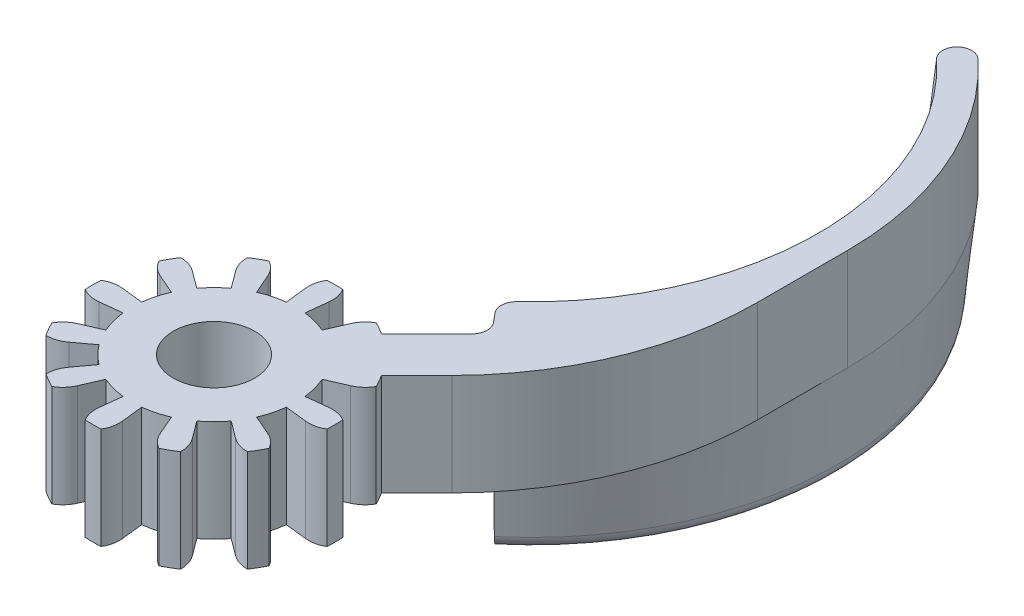
SolidWorks part; units mm, degrees
ref_plane "Plan de face" through (0, 0, 0) normal (0, 0, 1) x (1, 0, 0)
ref_plane "Plan de dessus" through (0, 0, 0) normal (0, 1, 0) x (1, 0, 0)
ref_plane "Plan de droite" through (0, 0, 0) normal (1, 0, 0) x (0, 0, -1)
sketch "Esquisse1" plane through (0, 0, 0) normal (0, 1, 0) x (1, 0, 0)
  line L0 (-18.0504, 0) -> (30.2368, 0) construction
  line L1 (0, 16.9051) -> (0, -14.3396) construction
  line L2 (0, 0) -> (-4.5652, 17.0374) construction
  line L51 (0, 0) -> (35.8316, 35.8316) construction
  line L52 (0, 0) -> (-1.8459, 16.2017) construction
  line L53 (-8.75, 40) -> (13.8918, 66.9834) construction
  line L54 (-8.75, 40) -> (13.2955, 13.7272) construction
  line L55 (-8.75, 40) -> (38.0168, 40) construction
  line L56 (10.1877, 62.5691) -> (7.9625, 59.9172)
  line L57 (10.9958, 16.4678) -> (7.9625, 20.0828)
  line L58 (22.25, 40) -> (22.25, -33.4016) construction
  line L59 (9.9946, 6.459) -> (13.4632, 9.9277)
  line L60 (6.459, 9.9946) -> (10.9074, 14.443)
  line L61 (17.25, 31.7709) -> (17.25, -36.5745) construction
  line L62 (22.25, 40) -> (22.25, 31.1409)
  line L65 (0, 0) -> (-1.1064, 16.8807) construction
  line L66 (-1.1547, 10.1344) -> (-0.9141, 8.0231)
  line L67 (1.1547, 10.1344) -> (0.9141, 8.0231)
  line L68 (4.0672, 9.354) -> (3.2199, 7.4053)
  line L70 (-8.75, 40) -> (-8.75, 0) construction
  line L72 (9.354, 4.0672) -> (7.4053, 3.2199)
  line L73 (10.1344, 1.1547) -> (8.0231, 0.9141)
  line L74 (10.1344, -1.1547) -> (8.0231, -0.9141)
  line L75 (9.354, -4.0672) -> (7.4053, -3.2199)
  line L76 (8.1993, -6.0672) -> (6.4911, -4.8032)
  line L77 (6.0672, -8.1993) -> (4.8032, -6.4911)
  line L78 (4.0672, -9.354) -> (3.2199, -7.4053)
  line L79 (1.1547, -10.1344) -> (0.9141, -8.0231)
  line L80 (-1.1547, -10.1344) -> (-0.9141, -8.0231)
  line L81 (-4.0672, -9.354) -> (-3.2199, -7.4053)
  line L82 (-6.0672, -8.1993) -> (-4.8032, -6.4911)
  line L83 (-8.1993, -6.0672) -> (-6.4911, -4.8032)
  line L84 (-9.354, -4.0672) -> (-7.4053, -3.2199)
  line L85 (-10.1344, -1.1547) -> (-8.0231, -0.9141)
  line L86 (-10.1344, 1.1547) -> (-8.0231, 0.9141)
  line L87 (-9.354, 4.0672) -> (-7.4053, 3.2199)
  line L88 (-8.1993, 6.0672) -> (-6.4911, 4.8032)
  line L89 (-6.0672, 8.1993) -> (-4.8032, 6.4911)
  line L90 (-4.0672, 9.354) -> (-3.2199, 7.4053)
  line L91 (6.0672, 8.1993) -> (4.8032, 6.4911)
  line L92 (8.1993, 6.0672) -> (6.4911, 4.8032)
  circle A0 centre (0, 0) radius 11.9 construction
  circle A26 centre (-8.75, 40) radius 25
  circle A27 centre (0, 0) radius 4
  arc A28 (7.9625, 59.9172) -> (7.9625, 20.0828) centre (-8.75, 40) cw
  arc A29 (12.3581, 62.7035) -> (22.25, 40) centre (-8.75, 40) cw
  circle A31 centre (0, 0) radius 8.075 construction
  circle A32 centre (0, 0) radius 10.2 construction
  arc A33 (-1.1547, 10.1344) -> (-0.7783, 11.8745) centre (1.6032, 10.4487) cw
  arc A34 (-0.9141, 8.0231) -> (-2.09, 7.7999) centre (0, 0) ccw
  arc A35 (0.7783, 11.8745) -> (-0.7783, 11.8745) centre (0, 0) ccw
  arc A36 (0.9141, 8.0231) -> (2.09, 7.7999) centre (0, 0) cw
  arc A37 (1.1547, 10.1344) -> (0.7783, 11.8745) centre (-1.6032, 10.4487) ccw
  arc A38 (3.2199, 7.4053) -> (2.09, 7.7999) centre (0, 0) ccw
  arc A39 (4.0672, 9.354) -> (5.2632, 10.6728) centre (6.6128, 8.2472) cw
  arc A40 (10.9074, 14.443) -> (10.9958, 16.4678) centre (9.8468, 15.5036) ccw
  arc A41 (5.2632, 10.6728) -> (6.459, 9.9946) centre (0, 0) cw
  arc A42 (9.9946, 6.459) -> (10.6728, 5.2632) centre (0, 0) cw
  arc A43 (13.4632, 9.9277) -> (22.25, 31.1409) centre (-7.75, 31.1409) ccw
  arc A46 (9.354, 4.0672) -> (10.6728, 5.2632) centre (8.2472, 6.6128) ccw
  arc A47 (7.4053, 3.2199) -> (7.7999, 2.09) centre (0, 0) cw
  arc A48 (8.0231, 0.9141) -> (7.7999, 2.09) centre (0, 0) ccw
  arc A49 (10.1344, 1.1547) -> (11.8745, 0.7783) centre (10.4487, -1.6032) cw
  arc A50 (11.8745, -0.7783) -> (11.8745, 0.7783) centre (0, 0) ccw
  arc A51 (10.1344, -1.1547) -> (11.8745, -0.7783) centre (10.4487, 1.6032) ccw
  arc A52 (8.0231, -0.9141) -> (7.7999, -2.09) centre (0, 0) cw
  arc A53 (7.4053, -3.2199) -> (7.7999, -2.09) centre (0, 0) ccw
  arc A54 (9.354, -4.0672) -> (10.6728, -5.2632) centre (8.2472, -6.6128) cw
  arc A55 (9.8945, -6.6113) -> (10.6728, -5.2632) centre (0, 0) ccw
  arc A56 (8.1993, -6.0672) -> (9.8945, -6.6113) centre (9.8504, -3.8359) ccw
  arc A57 (6.4911, -4.8032) -> (5.7099, -5.7099) centre (0, 0) cw
  arc A58 (4.8032, -6.4911) -> (5.7099, -5.7099) centre (0, 0) ccw
  arc A59 (6.0672, -8.1993) -> (6.6113, -9.8945) centre (3.8359, -9.8504) cw
  arc A60 (5.2632, -10.6728) -> (6.6113, -9.8945) centre (0, 0) ccw
  arc A61 (4.0672, -9.354) -> (5.2632, -10.6728) centre (6.6128, -8.2472) ccw
  arc A62 (3.2199, -7.4053) -> (2.09, -7.7999) centre (0, 0) cw
  arc A63 (0.9141, -8.0231) -> (2.09, -7.7999) centre (0, 0) ccw
  arc A64 (1.1547, -10.1344) -> (0.7783, -11.8745) centre (-1.6032, -10.4487) cw
  arc A65 (-0.7783, -11.8745) -> (0.7783, -11.8745) centre (0, 0) ccw
  arc A66 (-1.1547, -10.1344) -> (-0.7783, -11.8745) centre (1.6032, -10.4487) ccw
  arc A67 (-0.9141, -8.0231) -> (-2.09, -7.7999) centre (0, 0) cw
  arc A68 (-3.2199, -7.4053) -> (-2.09, -7.7999) centre (0, 0) ccw
  arc A69 (-4.0672, -9.354) -> (-5.2632, -10.6728) centre (-6.6128, -8.2472) cw
  arc A70 (-6.6113, -9.8945) -> (-5.2632, -10.6728) centre (0, 0) ccw
  arc A71 (-6.0672, -8.1993) -> (-6.6113, -9.8945) centre (-3.8359, -9.8504) ccw
  arc A72 (-4.8032, -6.4911) -> (-5.7099, -5.7099) centre (0, 0) cw
  arc A73 (-6.4911, -4.8032) -> (-5.7099, -5.7099) centre (0, 0) ccw
  arc A74 (-8.1993, -6.0672) -> (-9.8945, -6.6113) centre (-9.8504, -3.8359) cw
  arc A75 (-10.6728, -5.2632) -> (-9.8945, -6.6113) centre (0, 0) ccw
  arc A76 (-9.354, -4.0672) -> (-10.6728, -5.2632) centre (-8.2472, -6.6128) ccw
  arc A77 (-7.4053, -3.2199) -> (-7.7999, -2.09) centre (0, 0) cw
  arc A78 (-8.0231, -0.9141) -> (-7.7999, -2.09) centre (0, 0) ccw
  arc A79 (-10.1344, -1.1547) -> (-11.8745, -0.7783) centre (-10.4487, 1.6032) cw
  arc A80 (-11.8745, 0.7783) -> (-11.8745, -0.7783) centre (0, 0) ccw
  arc A81 (-10.1344, 1.1547) -> (-11.8745, 0.7783) centre (-10.4487, -1.6032) ccw
  arc A82 (-8.0231, 0.9141) -> (-7.7999, 2.09) centre (0, 0) cw
  arc A83 (-7.4053, 3.2199) -> (-7.7999, 2.09) centre (0, 0) ccw
  arc A84 (-9.354, 4.0672) -> (-10.6728, 5.2632) centre (-8.2472, 6.6128) cw
  arc A85 (-9.8945, 6.6113) -> (-10.6728, 5.2632) centre (0, 0) ccw
  arc A86 (-8.1993, 6.0672) -> (-9.8945, 6.6113) centre (-9.8504, 3.8359) ccw
  arc A87 (-6.4911, 4.8032) -> (-5.7099, 5.7099) centre (0, 0) cw
  arc A88 (-4.8032, 6.4911) -> (-5.7099, 5.7099) centre (0, 0) ccw
  arc A89 (-6.0672, 8.1993) -> (-6.6113, 9.8945) centre (-3.8359, 9.8504) cw
  arc A90 (-5.2632, 10.6728) -> (-6.6113, 9.8945) centre (0, 0) ccw
  arc A91 (-4.0672, 9.354) -> (-5.2632, 10.6728) centre (-6.6128, 8.2472) ccw
  arc A92 (-3.2199, 7.4053) -> (-2.09, 7.7999) centre (0, 0) cw
  arc A93 (6.0672, 8.1993) -> (6.6113, 9.8945) centre (3.8359, 9.8504) ccw
  arc A94 (4.8032, 6.4911) -> (5.7099, 5.7099) centre (0, 0) cw
  arc A95 (6.4911, 4.8032) -> (5.7099, 5.7099) centre (0, 0) ccw
  arc A96 (8.1993, 6.0672) -> (9.8945, 6.6113) centre (9.8504, 3.8359) cw
  arc A99 (12.3581, 62.7035) -> (10.1877, 62.5691) centre (11.3368, 61.6049) ccw
  arc A100 (6.6113, 9.8945) -> (5.2632, 10.6728) centre (0, 0) ccw
  arc A101 (10.6728, 5.2632) -> (9.8945, 6.6113) centre (0, 0) ccw
  point P14 (0, 11.9)
  point P37 (22.25, 18.7145)
  point P46 (17.25, 20.2855)
  point P52 (10.855, 16.6356)
  point P65 (17.25, 23.2668)
  point P90 (11.1764, 63.7474)
  point P133 (0, 0)
  point P170 (0, 0)
  dimension "D2" = 20.4
  dimension "D4" = 23.8
  dimension "D6" = 6.5
  dimension "D8" = 40
  dimension "D9" = 50
  dimension "D10" = 8
  dimension "D11" = 5
  dimension "D12" = 26
  dimension "D15" = 45
  dimension "D5" = 16.15
  dimension "D18" = 12
  dimension "D19" = 8.75
  dimension "D20" = 30
  dimension "D21" = 1.5
  dimension "D3" = 15
  dimension "D7" = 3.75
  dimension "D13" = 50
  dimension "D14" = 50
  dimension "D16" = 5
  dimension "D17" = 5
extrude "Boss.-Extru.1" add sketch "Esquisse1" along normal blind 10 contours A92 L90 A91 A90 A89 L89 A88 A87 L88 A86 A85 A84 L87 A83 A82 L86 A81 A80 A79 L85 A78 A77 L84 A76 A75 A74 L83 A73 A72 L82 A71 A70 A69 L81 A68 A67 L80 A66 A65 A64 L79 A63 A62 L78 A61 A60 A59 L77 A58 A57 L76
sketch "Esquisse2" plane through (0, 0, 0) normal (0, -1, 0) x (1, 0, 0)
  line L28 (22.25, -40) -> (22.25, -31.1409)
  line L29 (13.4632, -9.9277) -> (9.9946, -6.459)
  line L30 (9.354, -4.0672) -> (7.4053, -3.2199)
  line L31 (8.0231, -0.9141) -> (10.1344, -1.1547)
  line L32 (10.1344, 1.1547) -> (8.0231, 0.9141)
  line L33 (7.4053, 3.2199) -> (9.354, 4.0672)
  line L34 (8.1993, 6.0672) -> (6.4911, 4.8032)
  line L35 (4.8032, 6.4911) -> (6.0672, 8.1993)
  line L36 (4.0672, 9.354) -> (3.2199, 7.4053)
  line L37 (0.9141, 8.0231) -> (1.1547, 10.1344)
  line L38 (-1.1547, 10.1344) -> (-0.9141, 8.0231)
  line L39 (-3.2199, 7.4053) -> (-4.0672, 9.354)
  line L40 (-6.0672, 8.1993) -> (-4.8032, 6.4911)
  line L41 (-6.4911, 4.8032) -> (-8.1993, 6.0672)
  line L42 (-9.354, 4.0672) -> (-7.4053, 3.2199)
  line L43 (-8.0231, 0.9141) -> (-10.1344, 1.1547)
  line L44 (-10.1344, -1.1547) -> (-8.0231, -0.9141)
  line L45 (-7.4053, -3.2199) -> (-9.354, -4.0672)
  line L46 (-8.1993, -6.0672) -> (-6.4911, -4.8032)
  line L47 (-4.8032, -6.4911) -> (-6.0672, -8.1993)
  line L48 (-4.0672, -9.354) -> (-3.2199, -7.4053)
  line L49 (-0.9141, -8.0231) -> (-1.1547, -10.1344)
  line L50 (1.1547, -10.1344) -> (0.9141, -8.0231)
  line L51 (3.2199, -7.4053) -> (4.0672, -9.354)
  line L52 (6.459, -9.9946) -> (10.9074, -14.443)
  line L54 (10.9958, -16.4678) -> (7.9625, -20.0828)
  line L55 (7.9625, -59.9172) -> (10.1877, -62.5691)
  line L56 (22.25, -40) -> (22.25, -31.1409)
  line L57 (13.4632, -9.9277) -> (9.9946, -6.459)
  line L58 (9.354, -4.0672) -> (7.4053, -3.2199)
  line L59 (8.0231, -0.9141) -> (10.1344, -1.1547)
  line L60 (10.1344, 1.1547) -> (8.0231, 0.9141)
  line L61 (7.4053, 3.2199) -> (9.354, 4.0672)
  line L62 (8.1993, 6.0672) -> (6.4911, 4.8032)
  line L63 (4.8032, 6.4911) -> (6.0672, 8.1993)
  line L64 (4.0672, 9.354) -> (3.2199, 7.4053)
  line L65 (0.9141, 8.0231) -> (1.1547, 10.1344)
  line L66 (-1.1547, 10.1344) -> (-0.9141, 8.0231)
  line L67 (-3.2199, 7.4053) -> (-4.0672, 9.354)
  line L68 (-6.0672, 8.1993) -> (-4.8032, 6.4911)
  line L69 (-6.4911, 4.8032) -> (-8.1993, 6.0672)
  line L70 (-9.354, 4.0672) -> (-7.4053, 3.2199)
  line L71 (-8.0231, 0.9141) -> (-10.1344, 1.1547)
  line L72 (-10.1344, -1.1547) -> (-8.0231, -0.9141)
  line L73 (-7.4053, -3.2199) -> (-9.354, -4.0672)
  line L74 (-8.1993, -6.0672) -> (-6.4911, -4.8032)
  line L75 (-4.8032, -6.4911) -> (-6.0672, -8.1993)
  line L76 (-4.0672, -9.354) -> (-3.2199, -7.4053)
  line L77 (-0.9141, -8.0231) -> (-1.1547, -10.1344)
  line L78 (1.1547, -10.1344) -> (0.9141, -8.0231)
  line L79 (3.2199, -7.4053) -> (4.0672, -9.354)
  line L80 (6.459, -9.9946) -> (10.9074, -14.443)
  line L82 (10.9958, -16.4678) -> (7.9625, -20.0828)
  line L83 (7.9625, -59.9172) -> (10.1877, -62.5691)
  arc A0 (22.25, -40) -> (11.1561, -16.2356) centre (-8.75, -40) ccw
  arc A51 (10.9958, -16.4678) -> (10.9074, -14.443) centre (9.8468, -15.5036) ccw
  arc A52 (10.9958, -16.4678) -> (10.9074, -14.443) centre (9.8468, -15.5036) ccw
  arc A53 (12.3581, -62.7035) -> (22.25, -40) centre (-8.75, -40) ccw
  arc A54 (22.25, -31.1409) -> (13.4632, -9.9277) centre (-7.75, -31.1409) ccw
  arc A55 (9.9946, -6.459) -> (10.6728, -5.2632) centre (0, 0) ccw
  arc A56 (10.6728, -5.2632) -> (9.354, -4.0672) centre (8.2472, -6.6128) ccw
  arc A57 (7.4053, -3.2199) -> (8.0231, -0.9141) centre (0, 0) ccw
  arc A58 (10.1344, -1.1547) -> (11.8745, -0.7783) centre (10.4487, 1.6032) ccw
  arc A59 (11.8745, -0.7783) -> (11.8745, 0.7783) centre (0, 0) ccw
  arc A60 (11.8745, 0.7783) -> (10.1344, 1.1547) centre (10.4487, -1.6032) ccw
  arc A61 (8.0231, 0.9141) -> (7.4053, 3.2199) centre (0, 0) ccw
  arc A62 (9.354, 4.0672) -> (10.6728, 5.2632) centre (8.2472, 6.6128) ccw
  arc A63 (10.6728, 5.2632) -> (9.8945, 6.6113) centre (0, 0) ccw
  arc A64 (9.8945, 6.6113) -> (8.1993, 6.0672) centre (9.8504, 3.8359) ccw
  arc A65 (6.4911, 4.8032) -> (4.8032, 6.4911) centre (0, 0) ccw
  arc A66 (6.0672, 8.1993) -> (6.6113, 9.8945) centre (3.8359, 9.8504) ccw
  arc A67 (6.6113, 9.8945) -> (5.2632, 10.6728) centre (0, 0) ccw
  arc A68 (5.2632, 10.6728) -> (4.0672, 9.354) centre (6.6128, 8.2472) ccw
  arc A69 (3.2199, 7.4053) -> (0.9141, 8.0231) centre (0, 0) ccw
  arc A70 (1.1547, 10.1344) -> (0.7783, 11.8745) centre (-1.6032, 10.4487) ccw
  arc A71 (0.7783, 11.8745) -> (-0.7783, 11.8745) centre (0, 0) ccw
  arc A72 (-0.7783, 11.8745) -> (-1.1547, 10.1344) centre (1.6032, 10.4487) ccw
  arc A73 (-0.9141, 8.0231) -> (-3.2199, 7.4053) centre (0, 0) ccw
  arc A74 (-4.0672, 9.354) -> (-5.2632, 10.6728) centre (-6.6128, 8.2472) ccw
  arc A75 (-5.2632, 10.6728) -> (-6.6113, 9.8945) centre (0, 0) ccw
  arc A76 (-6.6113, 9.8945) -> (-6.0672, 8.1993) centre (-3.8359, 9.8504) ccw
  arc A77 (-4.8032, 6.4911) -> (-6.4911, 4.8032) centre (0, 0) ccw
  arc A78 (-8.1993, 6.0672) -> (-9.8945, 6.6113) centre (-9.8504, 3.8359) ccw
  arc A79 (-9.8945, 6.6113) -> (-10.6728, 5.2632) centre (0, 0) ccw
  arc A80 (-10.6728, 5.2632) -> (-9.354, 4.0672) centre (-8.2472, 6.6128) ccw
  arc A81 (-7.4053, 3.2199) -> (-8.0231, 0.9141) centre (0, 0) ccw
  arc A82 (-10.1344, 1.1547) -> (-11.8745, 0.7783) centre (-10.4487, -1.6032) ccw
  arc A83 (-11.8745, 0.7783) -> (-11.8745, -0.7783) centre (0, 0) ccw
  arc A84 (-11.8745, -0.7783) -> (-10.1344, -1.1547) centre (-10.4487, 1.6032) ccw
  arc A85 (-8.0231, -0.9141) -> (-7.4053, -3.2199) centre (0, 0) ccw
  arc A86 (-9.354, -4.0672) -> (-10.6728, -5.2632) centre (-8.2472, -6.6128) ccw
  arc A87 (-10.6728, -5.2632) -> (-9.8945, -6.6113) centre (0, 0) ccw
  arc A88 (-9.8945, -6.6113) -> (-8.1993, -6.0672) centre (-9.8504, -3.8359) ccw
  arc A89 (-6.4911, -4.8032) -> (-4.8032, -6.4911) centre (0, 0) ccw
  arc A90 (-6.0672, -8.1993) -> (-6.6113, -9.8945) centre (-3.8359, -9.8504) ccw
  arc A91 (-6.6113, -9.8945) -> (-5.2632, -10.6728) centre (0, 0) ccw
  arc A92 (-5.2632, -10.6728) -> (-4.0672, -9.354) centre (-6.6128, -8.2472) ccw
  arc A93 (-3.2199, -7.4053) -> (-0.9141, -8.0231) centre (0, 0) ccw
  arc A94 (-1.1547, -10.1344) -> (-0.7783, -11.8745) centre (1.6032, -10.4487) ccw
  arc A95 (-0.7783, -11.8745) -> (0.7783, -11.8745) centre (0, 0) ccw
  arc A96 (0.7783, -11.8745) -> (1.1547, -10.1344) centre (-1.6032, -10.4487) ccw
  arc A97 (0.9141, -8.0231) -> (3.2199, -7.4053) centre (0, 0) ccw
  arc A98 (4.0672, -9.354) -> (5.2632, -10.6728) centre (6.6128, -8.2472) ccw
  arc A99 (5.2632, -10.6728) -> (6.459, -9.9946) centre (0, 0) ccw
  arc A104 (7.9625, -59.9172) -> (7.9625, -20.0828) centre (-8.75, -40) ccw
  arc A105 (10.1877, -62.5691) -> (12.3581, -62.7035) centre (11.3368, -61.6049) ccw
  arc A106 (12.3581, -62.7035) -> (22.25, -40) centre (-8.75, -40) ccw
  arc A107 (22.25, -31.1409) -> (13.4632, -9.9277) centre (-7.75, -31.1409) ccw
  arc A108 (9.9946, -6.459) -> (10.6728, -5.2632) centre (0, 0) ccw
  arc A109 (10.6728, -5.2632) -> (9.354, -4.0672) centre (8.2472, -6.6128) ccw
  arc A110 (7.4053, -3.2199) -> (8.0231, -0.9141) centre (0, 0) ccw
  arc A111 (10.1344, -1.1547) -> (11.8745, -0.7783) centre (10.4487, 1.6032) ccw
  arc A112 (11.8745, -0.7783) -> (11.8745, 0.7783) centre (0, 0) ccw
  arc A113 (11.8745, 0.7783) -> (10.1344, 1.1547) centre (10.4487, -1.6032) ccw
  arc A114 (8.0231, 0.9141) -> (7.4053, 3.2199) centre (0, 0) ccw
  arc A115 (9.354, 4.0672) -> (10.6728, 5.2632) centre (8.2472, 6.6128) ccw
  arc A116 (10.6728, 5.2632) -> (9.8945, 6.6113) centre (0, 0) ccw
  arc A117 (9.8945, 6.6113) -> (8.1993, 6.0672) centre (9.8504, 3.8359) ccw
  arc A118 (6.4911, 4.8032) -> (4.8032, 6.4911) centre (0, 0) ccw
  arc A119 (6.0672, 8.1993) -> (6.6113, 9.8945) centre (3.8359, 9.8504) ccw
  arc A120 (6.6113, 9.8945) -> (5.2632, 10.6728) centre (0, 0) ccw
  arc A121 (5.2632, 10.6728) -> (4.0672, 9.354) centre (6.6128, 8.2472) ccw
  arc A122 (3.2199, 7.4053) -> (0.9141, 8.0231) centre (0, 0) ccw
  arc A123 (1.1547, 10.1344) -> (0.7783, 11.8745) centre (-1.6032, 10.4487) ccw
  arc A124 (0.7783, 11.8745) -> (-0.7783, 11.8745) centre (0, 0) ccw
  arc A125 (-0.7783, 11.8745) -> (-1.1547, 10.1344) centre (1.6032, 10.4487) ccw
  arc A126 (-0.9141, 8.0231) -> (-3.2199, 7.4053) centre (0, 0) ccw
  arc A127 (-4.0672, 9.354) -> (-5.2632, 10.6728) centre (-6.6128, 8.2472) ccw
  arc A128 (-5.2632, 10.6728) -> (-6.6113, 9.8945) centre (0, 0) ccw
  arc A129 (-6.6113, 9.8945) -> (-6.0672, 8.1993) centre (-3.8359, 9.8504) ccw
  arc A130 (-4.8032, 6.4911) -> (-6.4911, 4.8032) centre (0, 0) ccw
  arc A131 (-8.1993, 6.0672) -> (-9.8945, 6.6113) centre (-9.8504, 3.8359) ccw
  arc A132 (-9.8945, 6.6113) -> (-10.6728, 5.2632) centre (0, 0) ccw
  arc A133 (-10.6728, 5.2632) -> (-9.354, 4.0672) centre (-8.2472, 6.6128) ccw
  arc A134 (-7.4053, 3.2199) -> (-8.0231, 0.9141) centre (0, 0) ccw
  arc A135 (-10.1344, 1.1547) -> (-11.8745, 0.7783) centre (-10.4487, -1.6032) ccw
  arc A136 (-11.8745, 0.7783) -> (-11.8745, -0.7783) centre (0, 0) ccw
  arc A137 (-11.8745, -0.7783) -> (-10.1344, -1.1547) centre (-10.4487, 1.6032) ccw
  arc A138 (-8.0231, -0.9141) -> (-7.4053, -3.2199) centre (0, 0) ccw
  arc A139 (-9.354, -4.0672) -> (-10.6728, -5.2632) centre (-8.2472, -6.6128) ccw
  arc A140 (-10.6728, -5.2632) -> (-9.8945, -6.6113) centre (0, 0) ccw
  arc A141 (-9.8945, -6.6113) -> (-8.1993, -6.0672) centre (-9.8504, -3.8359) ccw
  arc A142 (-6.4911, -4.8032) -> (-4.8032, -6.4911) centre (0, 0) ccw
  arc A143 (-6.0672, -8.1993) -> (-6.6113, -9.8945) centre (-3.8359, -9.8504) ccw
  arc A144 (-6.6113, -9.8945) -> (-5.2632, -10.6728) centre (0, 0) ccw
  arc A145 (-5.2632, -10.6728) -> (-4.0672, -9.354) centre (-6.6128, -8.2472) ccw
  arc A146 (-3.2199, -7.4053) -> (-0.9141, -8.0231) centre (0, 0) ccw
  arc A147 (-1.1547, -10.1344) -> (-0.7783, -11.8745) centre (1.6032, -10.4487) ccw
  arc A148 (-0.7783, -11.8745) -> (0.7783, -11.8745) centre (0, 0) ccw
  arc A149 (0.7783, -11.8745) -> (1.1547, -10.1344) centre (-1.6032, -10.4487) ccw
  arc A150 (0.9141, -8.0231) -> (3.2199, -7.4053) centre (0, 0) ccw
  arc A151 (4.0672, -9.354) -> (5.2632, -10.6728) centre (6.6128, -8.2472) ccw
  arc A157 (7.9625, -59.9172) -> (7.9625, -20.0828) centre (-8.75, -40) ccw
  arc A158 (10.1877, -62.5691) -> (12.3581, -62.7035) centre (11.3368, -61.6049) ccw
  arc A160 (5.2632, -10.6728) -> (6.459, -9.9946) centre (0, 0) ccw
  dimension "D1" = 0
extrude "Boss.-Extru.2" add sketch "Esquisse2" along normal blind 10
chamfer "Chanfrein1" distance 20 angle 6.03 1 edges at (17.25, 10, -40)
fillet "Congé1" radius 1.5 2 edges at (8.6415, 0, -19.2736) (8.6415, 0, -60.7264)
chamfer "Chanfrein2" distance 10 angle 6.03 1 edges at (22.2396, -10, -39.1983)
fillet "Congé2" radius 1.5 1 edges at (21.1936, -10, -39.9603)
